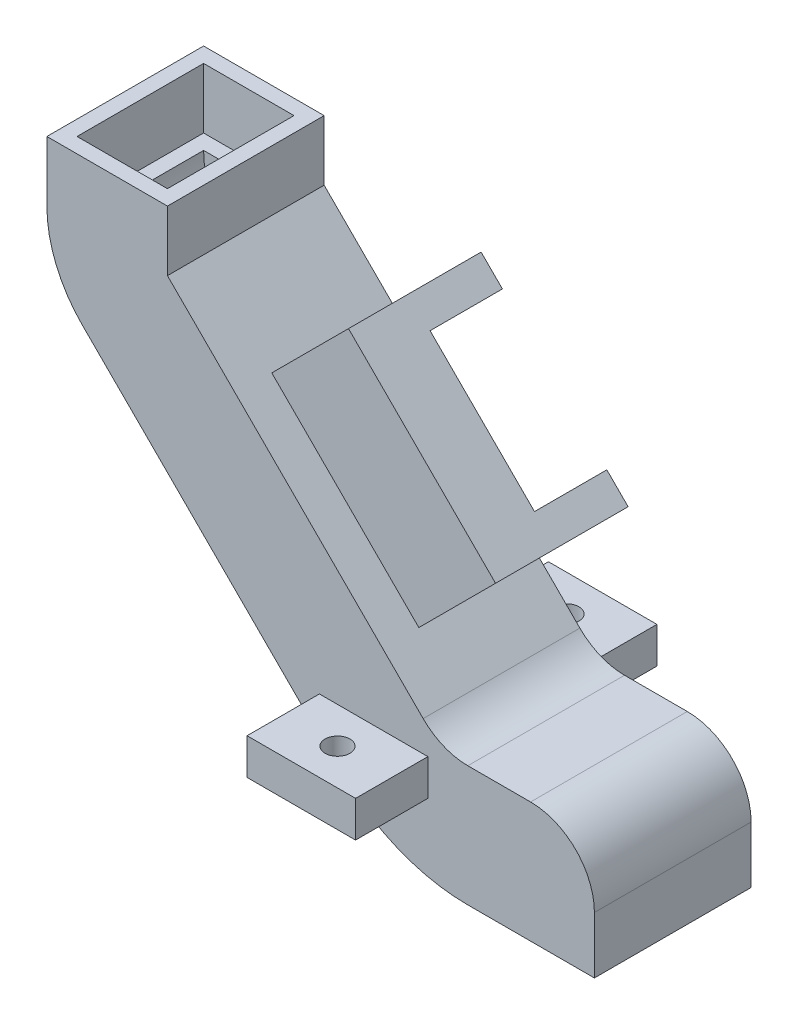
SolidWorks part; units mm, degrees
ref_plane "Front Plane" through (0, 0, 0) normal (0, 0, 1) x (1, 0, 0)
ref_plane "Top Plane" through (0, 0, 0) normal (0, 1, 0) x (1, 0, 0)
ref_plane "Right Plane" through (0, 0, 0) normal (1, 0, 0) x (0, 0, -1)
sketch "Sketch1" plane through (0, 0, 0) normal (0, 0, 1) x (1, 0, 0)
  line L0 (0, 0) -> (-44.5176, 44.5176) construction
  line L1 (-40.982, 48.0531) -> (-48.0531, 40.982) construction
  line L2 (-40.982, 48.0531) -> (1.4444, 5.6267)
  line L3 (12.3925, 6.0918) -> (22.8046, 6.0918)
  line L4 (-48.0531, 40.982) -> (-5.6267, -1.4444)
  line L5 (0, 0) -> (-7.0711, 0) construction
  line L6 (-40.982, 48.0531) -> (-37.4465, 51.5886) construction
  line L7 (-5.6267, -1.4444) -> (-9.1622, -4.9799) construction
  line L8 (12.3925, 1.0918) -> (22.8046, 1.0918)
  line L9 (-52.4465, 51.5886) -> (-57.4465, 51.5886)
  line L10 (-48.0531, 40.982) -> (-51.5886, 37.4465) construction
  line L11 (-51.5886, 37.4465) -> (-9.1622, -4.9799)
  line L12 (28.3925, -4.4961) -> (28.3925, -13.9082)
  line L13 (-42.4465, 51.5886) -> (-37.4465, 51.5886)
  line L14 (-37.4465, 51.5886) -> (4.9799, 9.1622)
  line L15 (4.9799, 9.1622) -> (1.4444, 5.6267) construction
  line L16 (12.3925, -8.9082) -> (12.3925, -13.9082)
  line L17 (12.3925, 16.5748) -> (4.9799, 9.1622) construction
  line L18 (-5.6267, -1.4444) -> (12.3925, 16.5748) construction
  line L19 (28.3925, -13.9082) -> (33.3925, -13.9082)
  line L20 (33.3925, -13.9082) -> (33.3925, -4.4961)
  arc A0 (-40.982, 48.0531) -> (-42.4465, 51.5886) centre (-37.4465, 51.5886) cw
  arc A1 (-5.6267, -1.4444) -> (12.3925, -8.9082) centre (12.3925, 16.5748) ccw
  arc A2 (-48.0531, 40.982) -> (-52.4465, 51.5886) centre (-37.4465, 51.5886) cw
  arc A3 (-9.1622, -4.9799) -> (12.3925, -13.9082) centre (12.3925, 16.5748) ccw
  arc A4 (-57.4465, 51.5886) -> (-51.5886, 37.4465) centre (-37.4465, 51.5886) ccw
  arc A5 (4.9799, 9.1622) -> (12.3925, 6.0918) centre (12.3925, 16.5748) ccw
  arc A6 (1.4444, 5.6267) -> (12.3925, 1.0918) centre (12.3925, 16.5748) ccw
  arc A7 (22.8046, 6.0918) -> (33.3925, -4.4961) centre (22.8046, -4.4961) cw
  arc A8 (22.8046, 1.0918) -> (28.3925, -4.4961) centre (22.8046, -4.4961) cw
  point P4 (-44.5176, 44.5176)
  dimension "D7" = 16
  dimension "D1" = 45
  dimension "D2" = 10
  dimension "D3" = 5
  dimension "D4" = 5
  dimension "D5" = 5
  dimension "D6" = 60
extrude "Boss-Extrude1" add sketch "Sketch1" along normal blind 16
sketch "Sketch5" plane through (0, 0, 16) normal (0, 0, 1) x (1, 0, 0)
  line L0 (-57.4465, 51.5886) -> (-37.4465, 51.5886)
  line L1 (-37.4465, 51.5886) -> (4.9799, 9.1622)
  line L2 (12.3925, 6.0918) -> (22.8046, 6.0918)
  line L3 (33.3925, -13.9082) -> (33.3925, -4.4961) construction
  line L4 (33.3925, -4.4961) -> (33.3925, -13.9082)
  line L5 (33.3925, -13.9082) -> (12.3925, -13.9082)
  line L6 (-9.1622, -4.9799) -> (-51.5886, 37.4465)
  arc A0 (4.9799, 9.1622) -> (12.3925, 6.0918) centre (12.3925, 16.5748) ccw
  arc A1 (22.8046, 6.0918) -> (33.3925, -4.4961) centre (22.8046, -4.4961) cw
  arc A2 (33.3925, -4.4961) -> (22.8046, 6.0918) centre (22.8046, -4.4961) ccw construction
  arc A3 (12.3925, -13.9082) -> (-9.1622, -4.9799) centre (12.3925, 16.5748) cw
  arc A4 (-51.5886, 37.4465) -> (-57.4465, 51.5886) centre (-37.4465, 51.5886) cw
extrude "Boss-Extrude4" add sketch "Sketch5" along normal blind 5
sketch "Sketch6" plane through (0, 0, 0) normal (0, 0, -1) x (-1, 0, 0)
  line L0 (-4.9799, 9.1622) -> (37.4465, 51.5886)
  line L1 (37.4465, 51.5886) -> (57.4465, 51.5886)
  line L2 (51.5886, 37.4465) -> (9.1622, -4.9799)
  line L3 (-12.3925, -13.9082) -> (-33.3925, -13.9082)
  line L4 (-33.3925, -13.9082) -> (-33.3925, -4.4961)
  line L5 (-22.8046, 6.0918) -> (-12.3925, 6.0918)
  line L6 (-22.8046, 6.0918) -> (-12.3925, 6.0918) construction
  line L7 (28.6077, 35.6787) -> (10.93, 18.001)
  line L8 (40.982, 48.0531) -> (-1.4444, 5.6267) construction
  line L9 (10.93, 18.001) -> (18.001, 10.93)
  line L10 (5.6267, -1.4444) -> (48.0531, 40.982) construction
  line L11 (18.001, 10.93) -> (35.6787, 28.6077)
  line L12 (35.6787, 28.6077) -> (28.6077, 35.6787)
  line L13 (40.982, 48.0531) -> (-1.4444, 5.6267) construction
  arc A0 (51.5886, 37.4465) -> (57.4465, 51.5886) centre (37.4465, 51.5886) ccw construction
  arc A1 (57.4465, 51.5886) -> (51.5886, 37.4465) centre (37.4465, 51.5886) cw
  arc A2 (9.1622, -4.9799) -> (-12.3925, -13.9082) centre (-12.3925, 16.5748) cw
  arc A3 (-33.3925, -4.4961) -> (-22.8046, 6.0918) centre (-22.8046, -4.4961) cw
  arc A4 (-12.3925, 6.0918) -> (-4.9799, 9.1622) centre (-12.3925, 16.5748) ccw construction
  arc A5 (-12.3925, 6.0918) -> (-4.9799, 9.1622) centre (-12.3925, 16.5748) ccw
  point P34 (19.7688, 26.8399)
  dimension "D1" = 25
extrude "Boss-Extrude5" add sketch "Sketch6" along normal blind 5
sketch "Sketch7" plane through (0, 51.5886, 0) normal (0, 1, 0) x (1, 0, 0)
  line L1 (-57.4465, 5) -> (-37.4465, 5)
  line L2 (-57.4465, 5) -> (-57.4465, -21)
  line L3 (-57.4465, -21) -> (-37.4465, -21)
  line L4 (-37.4465, 5) -> (-37.4465, -21)
  line L5 (-54.9465, 2.5) -> (-39.9465, 2.5)
  line L6 (-54.9465, 2.5) -> (-54.9465, -18.5)
  line L7 (-54.9465, -18.5) -> (-39.9465, -18.5)
  line L8 (-39.9465, 2.5) -> (-39.9465, -18.5)
  dimension "D1" = 2.5
  dimension "D2" = 2.5
  dimension "D3" = 2.5
  dimension "D4" = 2.5
extrude "Boss-Extrude6" add sketch "Sketch7" along normal blind 10
sketch "Sketch9" plane through (7.0711, 7.0711, 0) normal (0.7071, 0.7071, 0) x (0, 0, -1)
  line L0 (-15, 32.9573) -> (-5, 32.9573) construction
  line L1 (-15, 46.9573) -> (-5, 46.9573)
  line L2 (-15, 46.9573) -> (-15, 12.4573)
  line L3 (-15, 12.4573) -> (-5, 12.4573)
  line L4 (-5, 46.9573) -> (-5, 12.4573)
  line L5 (5, 62.9573) -> (5, 2.9573) construction
  point P8 (5, 32.9573)
  dimension "D1" = 34.5
  dimension "D2" = 20.5
  dimension "D3" = 10
  dimension "D4" = 10
extrude "Boss-Extrude7" add sketch "Sketch9" along normal blind 18
sketch "Sketch10" plane through (0, 0, 5) normal (0, 0, -1) x (-1, 0, 0)
  line L0 (20.8295, 45.5782) -> (17.2939, 42.0427)
  line L1 (13.4049, 53.0028) -> (26.1328, 40.2749) construction
  line L2 (17.2939, 42.0427) -> (9.8693, 49.4673)
  line L3 (-10.9903, 28.6077) -> (13.4049, 53.0028) construction
  line L4 (9.8693, 49.4673) -> (13.4049, 53.0028)
  line L5 (13.4049, 53.0028) -> (20.8295, 45.5782)
  line L6 (-10.9903, 28.6077) -> (-7.4548, 32.1432)
  line L7 (-7.4548, 32.1432) -> (-0.0302, 24.7186)
  line L8 (-0.0302, 24.7186) -> (-3.5657, 21.183)
  line L9 (-10.9903, 28.6077) -> (1.7376, 15.8797) construction
  line L10 (-3.5657, 21.183) -> (-10.9903, 28.6077)
  line L11 (-0.0302, 24.7186) -> (17.2939, 42.0427) construction
  line L13 (10.5764, 35.3252) -> (3.1518, 42.7498) construction
  line L14 (1.7376, 15.8797) -> (26.1328, 40.2749) construction
  point P20 (-3.7425, 28.4309)
  dimension "D1" = 5
  dimension "D2" = 5
  dimension "D3" = 10.5
  dimension "D5" = 15
  dimension "D6" = 7.5
extrude "Boss-Extrude8" add sketch "Sketch10" along normal blind 12
sketch "Sketch11" plane through (0, 0, -5) normal (0, 0, -1) x (-1, 0, 0)
  line L0 (19.7688, 26.8399) -> (14.3563, 32.2524) construction
  line L1 (40.982, 48.0531) -> (-1.4444, 5.6267) construction
  line L2 (24.365, 31.4361) -> (20.8295, 34.9716)
  line L3 (1.7376, 15.8797) -> (26.1328, 40.2749) construction
  line L5 (20.8295, 34.9716) -> (16.2333, 30.3754)
  line L6 (24.365, 31.4361) -> (19.7688, 26.8399)
  line L7 (9.8693, 49.4673) -> (17.2939, 42.0427) construction
  line L8 (16.2333, 30.3754) -> (9.5158, 23.6579)
  line L9 (9.5158, 23.6579) -> (13.0513, 20.1224)
  line L10 (13.0513, 20.1224) -> (19.7688, 26.8399)
  point P10 (11.2835, 21.8901)
  dimension "D1" = 6.5
  dimension "D2" = 9.5
extrude "Cut-Extrude3" cut sketch "Sketch11" against normal up to surface (10 mm away) up to face at (-8.1016, 33.911, 5)
sketch "Sketch12" plane through (0, 0, 21) normal (0, 0, 1) x (1, 0, 0)
  line L0 (16.0503, -1.9082) -> (-12.234, -1.9082) construction
  line L4 (-26.1328, 40.2749) -> (-1.7376, 15.8797) construction
  line L5 (-51.5886, 37.4465) -> (-9.1622, -4.9799) construction
  line L6 (-12.234, -1.9082) -> (5.766, -1.9082)
  line L7 (5.766, -1.9082) -> (5.766, 4.0918)
  line L8 (5.766, 4.0918) -> (-12.234, 4.0918)
  line L9 (-12.234, 4.0918) -> (-12.234, -1.9082)
  line L10 (12.3925, -13.9082) -> (33.3925, -13.9082) construction
  dimension "D1" = 18
  dimension "D2" = 6
  dimension "D3" = 12
extrude "Boss-Extrude9" add sketch "Sketch12" along normal blind 12
sketch "Sketch13" plane through (0, 4.0918, 0) normal (0, 1, 0) x (1, 0, 0)
  line L0 (5.766, -33) -> (-12.234, -33) construction
  line L1 (5.766, -33) -> (5.766, -21) construction
  circle A0 centre (-3.234, -27) radius 2.0625
  point P5 (-3.234, -33)
  point P9 (5.766, -27)
  dimension "D1" = 4.125
extrude "Cut-Extrude4" cut sketch "Sketch13" against normal blind 18
sketch "Sketch14" plane through (0, 0, 0) normal (0, 1, 0) x (1, 0, 0)
  line L0 (28.3925, -8) -> (12.3925, -8) construction
  line L1 (12.3925, -21) -> (33.3925, -21) construction
  line L2 (28.3925, -16) -> (28.3925, 0) construction
  line L3 (-3.234, -27) -> (20.3925, -27) construction
  line L4 (12.3925, -16) -> (12.3925, 0) construction
  line L6 (20.3925, -8) -> (20.3925, -27) construction
  dimension "D1" = 23.6265
  dimension "D2" = 19
  dimension "D3" = 13
ref_plane "Plane1" through (0, 0, 8) normal (0, 0, 1) x (1, 0, 0)
mirror "Mirror1" about plane through (0, 0, 8) normal (0, 0, 1) of "Cut-Extrude4", "Boss-Extrude9"
